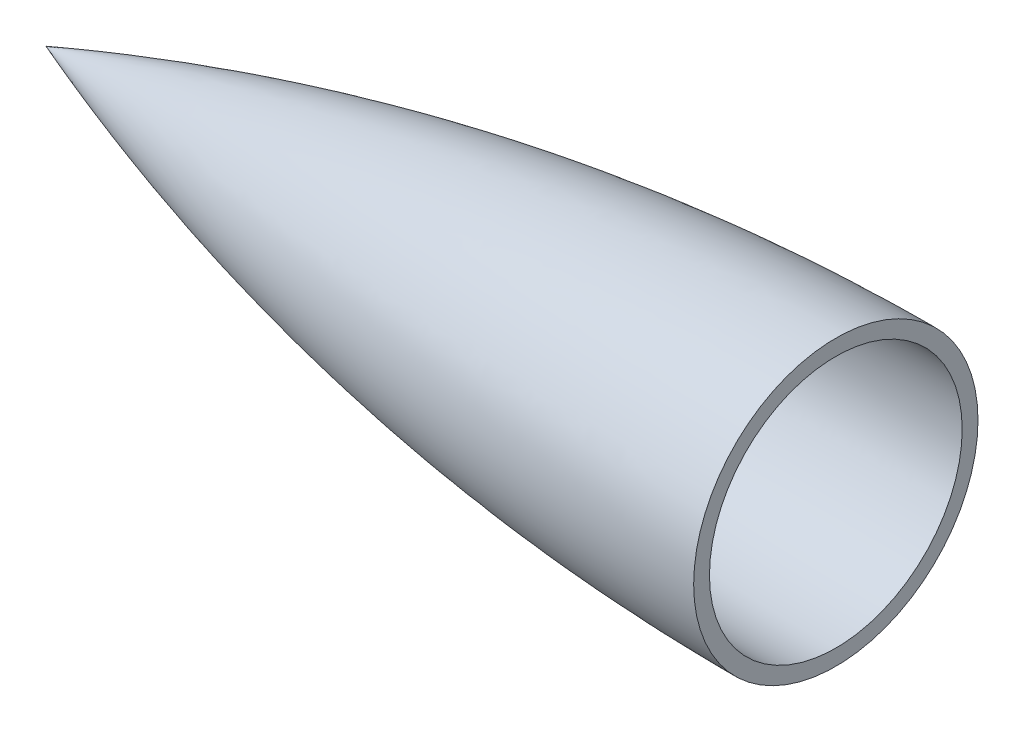
SolidWorks part; units mm, degrees
material "Fibre de verre A"
ref_plane "Plan de face" through (0, 0, 0) normal (0, 0, 1) x (1, 0, 0)
ref_plane "Plan de dessus" through (0, 0, 0) normal (0, 1, 0) x (1, 0, 0)
ref_plane "Plan de droite" through (0, 0, 0) normal (1, 0, 0) x (0, 0, -1)
sketch "Esquisse1" plane through (0, 0, 0) normal (0, 1, 0) x (1, 0, 0)
  line L0 (0, 0) -> (301.6119, 0) construction
  line L1 (250, 45) -> (250, 0)
  line L2 (250, 0) -> (0, 0) construction
  line L3 (250, 0) -> (0, 0)
  line L4 (-54.2063, 0) -> (320.9698, 0) construction
  spline S0 degree 4 poles (-23.75, -9.3206) (-23.3793, -9.1675) (-22.6378, -8.8618) (-21.1533, -8.2524) (-18.9254, -7.3456) (-16.3195, -6.2962) (-13.3492, -5.1155) (-10.3763, -3.9492) (-7.7868, -2.9463) (-5.5576, -2.0927) (-3.7137, -1.3926) (-2.2648, -0.8461) (-0.1075, -0.0388) (0.8923, 0.3317) (3.5178, 1.3014) (4.8595, 1.7876) (6.481, 2.3772) (7.8299, 2.8619) (9.2895, 3.3843) (11.7855, 4.2708) (14.6616, 5.279) (17.8907, 6.3927) (22.2119, 7.856) (26.5382, 9.2938) (31.5993, 10.9361) (37.3979, 12.7636) (43.2125, 14.542) (49.0415, 16.271) (56.3462, 18.3703) (65.1397, 20.7903) (73.9667, 23.0858) (82.8251, 25.2563) (90.227, 26.9814) (96.16, 28.3112) (103.5901, 29.9105) (112.5275, 31.7288) (121.4898, 33.4206) (130.475, 34.9856) (139.4772, 36.4488) (148.4954, 37.8102) (157.5322, 39.0439) (166.5854, 40.1499) (174.1395, 40.9861) (180.1882, 41.6038) (186.242, 42.1702) (192.3004, 42.6852) (197.6051, 43.0908) (202.1542, 43.4064) (205.9467, 43.648) (208.9814, 43.8283) (212.0168, 43.9958) (215.053, 44.1504) (218.0897, 44.2922) (221.1271, 44.4211) (224.165, 44.5371) (227.2032, 44.6402) (230.242, 44.7304) (233.281, 44.8077) (235.9407, 44.8641) (238.2201, 44.9044) (240.1205, 44.9326) (241.6389, 44.9519) (243.1631, 44.968) (244.6703, 44.9809) (246.2317, 44.9906) (247.6173, 44.997) (249.5342, 45.0003) (250.4911, 45.0003) (252.4435, 44.9969) (253.8441, 44.9902) (255.4491, 44.9801) (256.9849, 44.9666) (258.9327, 44.9456) (261.2684, 44.9135) (264.0075, 44.866) (267.1406, 44.7979) (269.8924, 44.7261) (272.2495, 44.6559) (273.8214, 44.6045) (274.6071, 44.5777) (275, 44.564) knots 0 0 0 0 0 0.005245 0.010489 0.020979 0.031468 0.041958 0.052322 0.062685 0.067867 0.073049 0.078231 0.083413 0.093352 0.098321 0.10329 0.108259 0.113229 0.118198 0.123167 0.143044 0.152983 0.162922 0.182799 0.202676 0.222553 0.24243 0.262307 0.282185 0.321939 0.361693 0.38157 0.401447 0.421325 0.441202 0.480956 0.52071 0.540588 0.560465 0.600219 0.639973 0.65985 0.679728 0.699605 0.719482 0.739359 0.759236 0.769175 0.779113 0.789052 0.798991 0.808929 0.818868 0.828806 0.838745 0.848683 0.858622 0.868561 0.878499 0.883468 0.888438 0.893407 0.898376 0.903346 0.908315 0.913284 0.918253 0.923331 0.928409 0.933486 0.938564 0.943642 0.948719 0.958874 0.969156 0.979437 0.989719 0.994859 1 1 1 1 1 construction
  spline S1 degree 4 poles (0, 0) (0.5947, 0.2212) (1.4352, 0.5323) (3.5178, 1.3014) (4.8595, 1.7876) (6.481, 2.3772) (7.8299, 2.8619) (9.2895, 3.3843) (11.7855, 4.2708) (14.6616, 5.279) (17.8907, 6.3927) (22.2119, 7.856) (26.5382, 9.2938) (31.5993, 10.9361) (37.3979, 12.7636) (43.2125, 14.542) (49.0415, 16.271) (56.3462, 18.3703) (65.1397, 20.7903) (73.9667, 23.0858) (82.8251, 25.2563) (90.227, 26.9814) (96.16, 28.3112) (103.5901, 29.9105) (112.5275, 31.7288) (121.4898, 33.4206) (130.475, 34.9856) (139.4772, 36.4488) (148.4954, 37.8102) (157.5322, 39.0439) (166.5854, 40.1499) (174.1395, 40.9861) (180.1882, 41.6038) (186.242, 42.1702) (192.3004, 42.6852) (197.6051, 43.0908) (202.1542, 43.4064) (205.9467, 43.648) (208.9814, 43.8283) (212.0168, 43.9958) (215.053, 44.1504) (218.0897, 44.2922) (221.1271, 44.4211) (224.165, 44.5371) (227.2032, 44.6402) (230.242, 44.7304) (233.281, 44.8077) (235.9407, 44.8641) (238.2201, 44.9044) (240.1205, 44.9326) (241.6389, 44.9519) (243.1631, 44.968) (244.6703, 44.9809) (246.2317, 44.9906) (247.6173, 44.997) (249.0472, 44.9995) (249.6828, 45) (250, 45) knots 0.083413 0.083413 0.083413 0.083413 0.083413 0.093352 0.098321 0.10329 0.108259 0.113229 0.118198 0.123167 0.143044 0.152983 0.162922 0.182799 0.202676 0.222553 0.24243 0.262307 0.282185 0.321939 0.361693 0.38157 0.401447 0.421325 0.441202 0.480956 0.52071 0.540588 0.560465 0.600219 0.639973 0.65985 0.679728 0.699605 0.719482 0.739359 0.759236 0.769175 0.779113 0.789052 0.798991 0.808929 0.818868 0.828806 0.838745 0.848683 0.858622 0.868561 0.878499 0.883468 0.888438 0.893407 0.898376 0.903346 0.908315 0.913284 0.918253 0.918253 0.918253 0.918253 0.918253
  dimension "D1" = 250
  dimension "D2" = 45
revolve "Révolution1" add sketch "Esquisse1" angle 360 about L3
shell "Coque4" thickness 5 removed face at (250, 0, -45)
sketch "Esquisse2" plane through (250, 0, 0) normal (1, 0, 0) x (0, 0, -1)
sketch "Esquisse3" plane through (250, 0, 0) normal (1, 0, 0) x (0, 0, -1)
  circle A0 centre (0, 0) radius 40
  circle A1 centre (0, 0) radius 42
  dimension "D1" = 84
  dimension "D2" = 80
